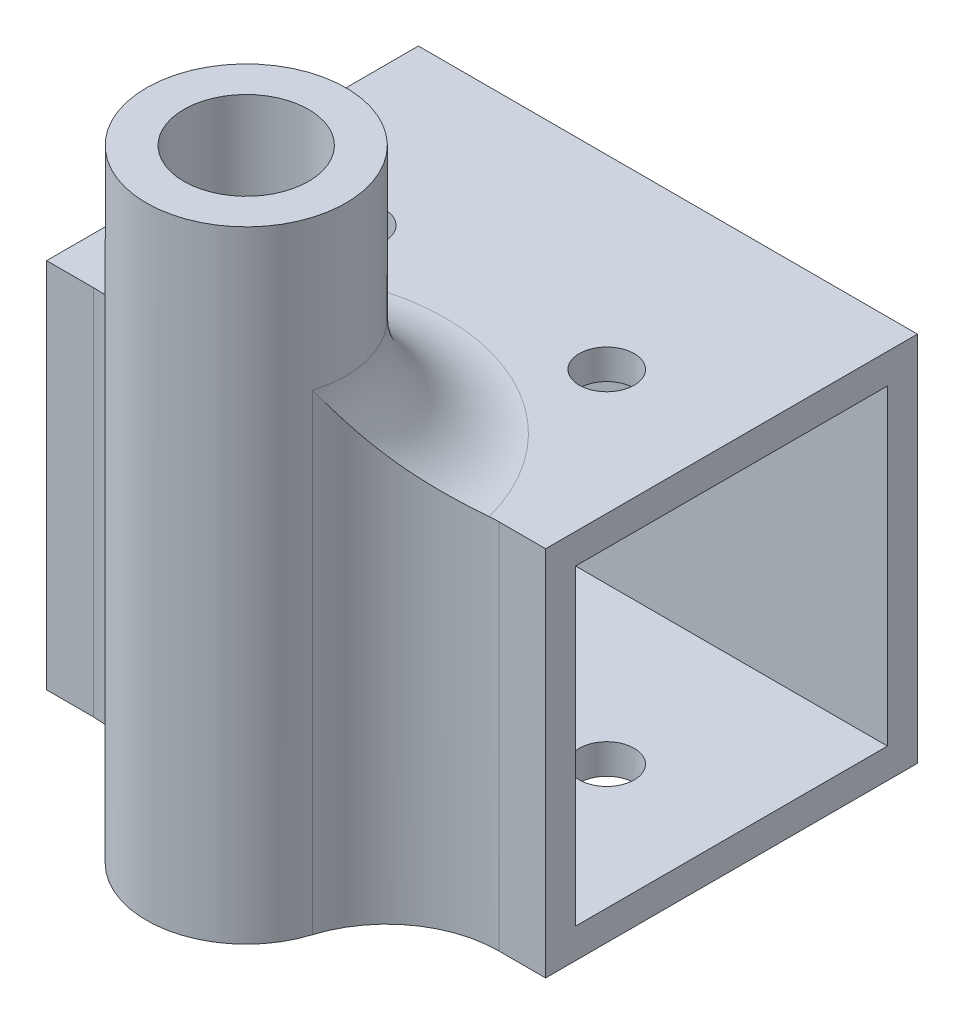
SolidWorks part; units mm, degrees
ref_plane "Front" through (0, 0, 0) normal (0, 0, 1) x (1, 0, 0)
ref_plane "Top" through (0, 0, 0) normal (0, 1, 0) x (1, 0, 0)
ref_plane "Right" through (0, 0, 0) normal (1, 0, 0) x (0, 0, -1)
sketch "Эскиз1" plane through (0, 0, 0) normal (1, 0, 0) x (0, 0, -1)
  line L1 (-12.5, -12.5) -> (12.5, -12.5)
  line L2 (-12.5, -12.5) -> (-12.5, 12.5)
  line L3 (-12.5, 12.5) -> (12.5, 12.5)
  line L4 (12.5, -12.5) -> (12.5, 12.5)
  line L5 (-12.5, -12.5) -> (12.5, 12.5) construction
  line L6 (-12.5, 12.5) -> (12.5, -12.5) construction
  point P0 (0, 0)
  dimension "D1" = 25
  dimension "D2" = 25
extrude "Вытянуть-Тонкостенный1" add sketch "Эскиз1" along normal blind 40 thin thin type one direction wall 2.4
sketch "Эскиз2" plane through (0, 14.9, 0) normal (0, 1, 0) x (1, 0, 0)
  line L0 (20, 14.9) -> (20, -40.7195) construction
  line L1 (40, 14.9) -> (0, 14.9) construction
  line L2 (40, -14.9) -> (0, -14.9) construction
  circle A0 centre (20, -18.9) radius 5
  circle A1 centre (20, -18.9) radius 8
  dimension "D1" = 4
extrude "Бобышка-Вытянуть1" add sketch "Эскиз2" against normal up to surface (29.8 mm away) and the other way blind 20 up to face at (20, -14.9, 0)
fillet "Скругление1" radius 9 2 edges at (26.9282, 0, 14.9) (13.0718, 0, 14.9)
sketch "Эскиз4" plane through (0, -14.9, 0) normal (0, 1, 0) x (1, 0, 0)
  line L0 (0, 0) -> (40, 0) construction
  line L1 (40, 14.9) -> (40, -14.9) construction
  line L2 (0, 14.9) -> (0, -14.9) construction
  circle A0 centre (10, 0) radius 2.2
  circle A1 centre (30, 0) radius 2.2
  dimension "D1" = 10
  dimension "D2" = 10
extrude "Вырез-Вытянуть1" cut sketch "Эскиз4" along normal through all
sketch "Эскиз5" plane through (0, 14.9, 0) normal (0, 1, 0) x (1, 0, 0)
  circle A0 centre (20, -18.9) radius 5
extrude "Вырез-Вытянуть2" cut sketch "Эскиз5" against normal up to next
sketch "Эскиз6" plane through (0, 0, 0) normal (-1, 0, 0) x (0, 0, 1)
  line L1 (12.5, -12.5) -> (-12.5, -12.5)
  line L2 (12.5, -12.5) -> (12.5, 12.5)
  line L3 (12.5, 12.5) -> (-12.5, 12.5)
  line L4 (-12.5, -12.5) -> (-12.5, 12.5)
extrude "Вырез-Вытянуть3" cut sketch "Эскиз6" against normal up to next
fillet "Скругление2" radius 8 1 edges at (20, 14.9, 10.9)
